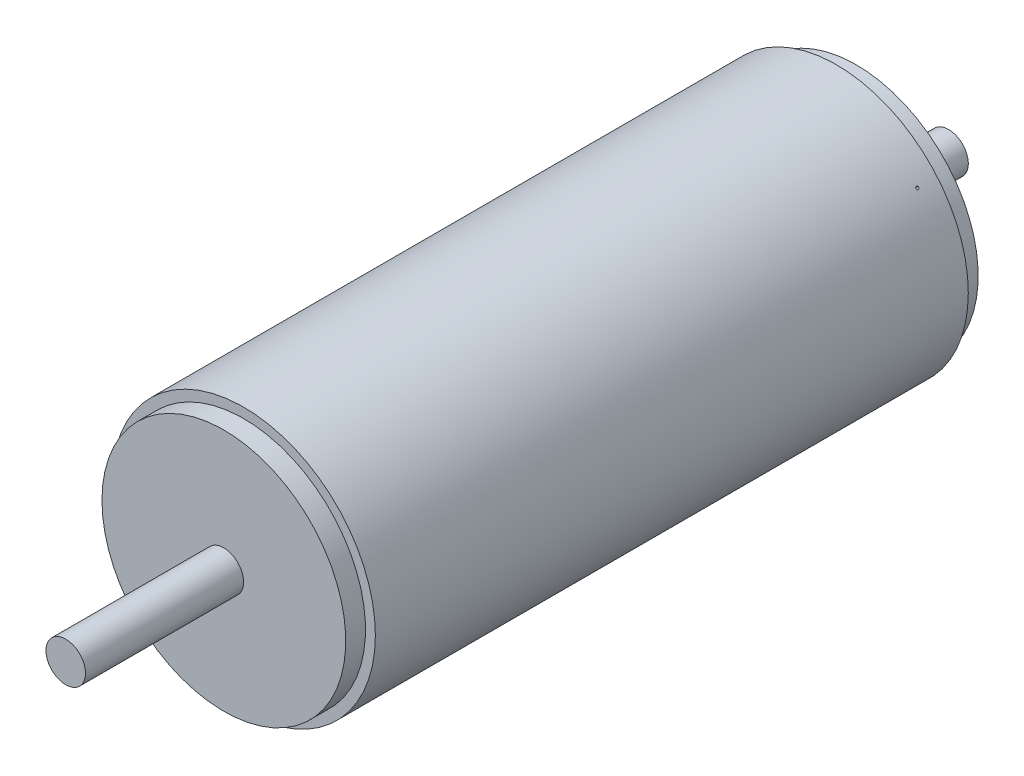
SolidWorks part; units mm, degrees
ref_plane "Front Plane" through (0, 0, 0) normal (0, 0, 1) x (1, 0, 0)
ref_plane "Top Plane" through (0, 0, 0) normal (0, 1, 0) x (1, 0, 0)
ref_plane "Right Plane" through (0, 0, 0) normal (1, 0, 0) x (0, 0, -1)
sketch "Sketch1" plane through (0, 0, 0) normal (0, 0, 1) x (1, 0, 0)
  circle A0 centre (0, 0) radius 100
  dimension "D1" = 200
extrude "Boss-Extrude1" add sketch "Sketch1" along normal blind 450
sketch "Sketch2" plane through (0, 0, 0) normal (0, 0, -1) x (-1, 0, 0)
  circle A0 centre (0, 0) radius 92.5
  circle A1 centre (0, 0) radius 100 construction
  dimension "D1" = 7.5
extrude "Boss-Extrude2" add sketch "Sketch2" along normal blind 15
sketch "Sketch3" plane through (0, 0, -15) normal (0, 0, -1) x (-1, 0, 0)
  circle A0 centre (0, 0) radius 15
  dimension "D1" = 30
extrude "Boss-Extrude3" add sketch "Sketch3" along normal blind 70
ref_plane "Plane1" through (0, 0, 225) normal (0, 0, -1) x (-1, 0, 0)
mirror "Mirror1" about plane through (0, 0, 225) normal (0, 0, -1) of "Boss-Extrude2"
sketch "Sketch4" plane through (0, 0, 465) normal (0, 0, 1) x (1, 0, 0)
  circle A0 centre (0, 0) radius 15
  dimension "D1" = 30
extrude "Boss-Extrude4" add sketch "Sketch4" along normal blind 120
ref_axis "Axis1" through (0, 0, 450) along (0, 0, -1)
sketch3d "3DSketch1"
  point P0 (0, 154.6954, 37.3179)
ref_plane "Plane5" through (0, 0, 15) normal (0, 0, -1) x (-1, 0, 0)
ref_plane "Plane6" through (76.2972, 64.6432, 0) normal (0.763, 0.6464, 0) x (0, 0, -1)
sketch "Sketch5" plane through (76.2972, 64.6432, 0) normal (0.763, 0.6464, 0) x (0, 0, -1)
  line L0 (-15, -110) -> (-15, 110) construction
  line L1 (-450, 0) -> (0, 0) construction
  circle A0 centre (-15, 0) radius 1
  dimension "D1" = 2
extrude "Cut-Extrude1" cut sketch "Sketch5" against normal blind 3
